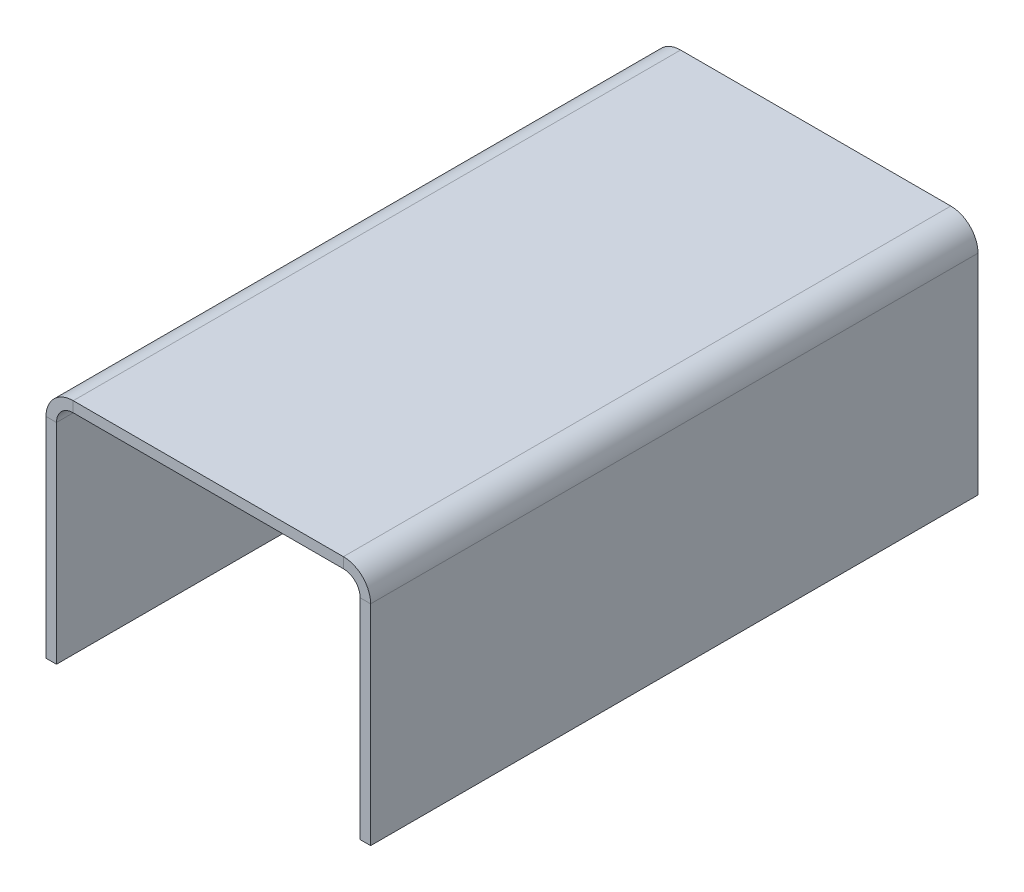
SolidWorks part; units mm, degrees
note: The reader was unsure of these and kept them because the rebuilt part matched: flange length of "Edge-Flange1".
material "ASTM A36 Steel"
ref_plane "Front Plane" through (0, 0, 0) normal (0, 0, 1) x (1, 0, 0)
ref_plane "Top Plane" through (0, 0, 0) normal (0, 1, 0) x (1, 0, 0)
ref_plane "Right Plane" through (0, 0, 0) normal (1, 0, 0) x (0, 0, -1)
sketch "Sketch1" plane through (0, 0, 0) normal (0, 1, 0) x (1, 0, 0)
  line L1 (-77.5, -145) -> (77.5, -145)
  line L2 (-77.5, -145) -> (-77.5, 145)
  line L3 (-77.5, 145) -> (77.5, 145)
  line L4 (77.5, -145) -> (77.5, 145)
  line L5 (-77.5, -145) -> (77.5, 145) construction
  line L6 (-77.5, 145) -> (77.5, -145) construction
  point P0 (0, 0)
  dimension "D1" = 155
  dimension "D2" = 290
base flange "Base-Flange1" sketch "Sketch1" thickness 5 reverse thickness direction no parameters "D1"=0.7366
edge flange "Edge-Flange1" sketch "Sketch10" flange profiles "Sketch10", "Sketch11" flange angle 90 flange length 113 flange position material inside bend radius 8 thickness 5 relief rectangular parameters "D6"=10, "D8"=1
sketch "Sketch10" plane through (77.5, -5, 0) normal (1, 0, 0) x (0, 0, 1)
  line L0 (145, 0) -> (-145, 0) construction
  line L1 (145, 0) -> (-145, 0)
  line L2 (-145, 0) -> (-145, 108)
  line L3 (-145, 108) -> (145, 108)
  line L4 (145, 108) -> (145, 0)
sketch "Sketch11" plane through (-77.5, -5, 0) normal (-1, 0, 0) x (0, 0, -1)
  line L0 (145, 0) -> (-145, 0) construction
  line L1 (145, 0) -> (-145, 0)
  line L2 (-145, 0) -> (-145, 108)
  line L3 (-145, 108) -> (145, 108)
  line L4 (145, 108) -> (145, 0)
bend "EdgeBend1" bend radius 8 bend angle 90 parameters "D5"=1
bend "EdgeBend2" bend radius 8 bend angle 90 parameters "D5"=2
sketch "Bend-Lines1" [suppressed] plane through (0, 0, 0) normal (0, 1, 0) x (1, 0, 0)
sketch "Bounding-Box1" [suppressed] plane through (0, 0, 0) normal (0, 1, 0) x (1, 0, 0)
sheet metal parameters "Sheet-Metal2" thickness 5 parameters "D1"=0.7366
flat pattern "Flat-Pattern2" [suppressed]
sketch "Bend-Lines2" plane through (0, 0, 0) normal (0, 1, 0) x (1, 0, 0)
sketch3d "Bounding-Box2" [suppressed]
  line L0 (77.5, -142.5, 0) -> (77.5, 142.5, 0) construction
  line L1 (-77.5, -142.5, 0) -> (-77.5, 142.5, 0) construction
  line L2 (77.5, -142.5, 0) -> (-77.5, -142.5, 0) construction
  line L3 (77.5, 142.5, 0) -> (-77.5, 142.5, 0) construction
sheet metal parameters "Sheet-Metal3" thickness 5 parameters "D1"=0.7366
flat pattern "Flat-Pattern2"
sketch "Bend-Lines2" plane through (0, 0, 0) normal (0, 1, 0) x (1, 0, 0)
  line L0 (-72.7467, 145) -> (-72.7467, -145) construction
  line L1 (72.7467, -145) -> (72.7467, 145) construction
  line L2 (-72.7467, 145) -> (-72.7467, -145) construction
  line L3 (72.7467, -145) -> (72.7467, 145) construction
sketch3d "Bounding-Box2" [suppressed]
  line L0 (180.9934, 145, 0) -> (-180.9934, 145, 0) construction
  line L1 (180.9934, -145, 0) -> (-180.9934, -145, 0) construction
  line L2 (180.9934, 145, 0) -> (180.9934, -145, 0) construction
  line L3 (-180.9934, 145, 0) -> (-180.9934, -145, 0) construction
bend of the flat pattern "Flatten-<EdgeBend1>1"
bend of the flat pattern "Flatten-<EdgeBend2>1"
